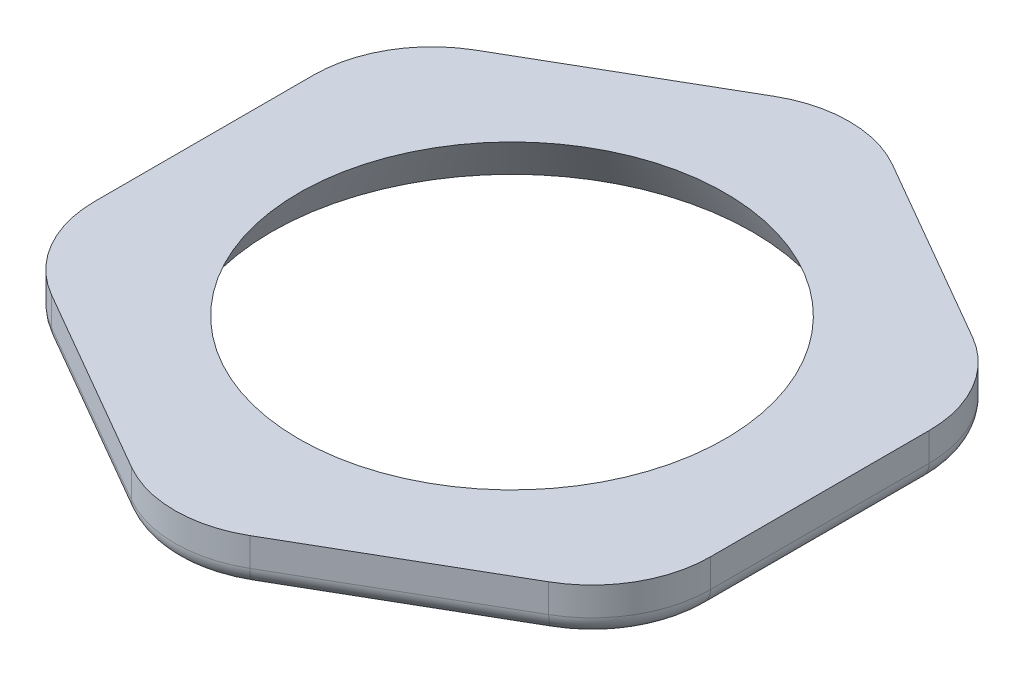
SolidWorks part; units mm, degrees
ref_plane "Front Plane" through (0, 0, 0) normal (0, 0, 1) x (1, 0, 0)
ref_plane "Top Plane" through (0, 0, 0) normal (0, 1, 0) x (1, 0, 0)
ref_plane "Right Plane" through (0, 0, 0) normal (1, 0, 0) x (0, 0, -1)
sketch "Sketch1" plane through (0, 0, 0) normal (0, 1, 0) x (1, 0, 0)
  line L1 (6.5, -2.3094) -> (6.5, 2.3094)
  line L2 (5.25, 4.4745) -> (1.25, 6.7839)
  line L3 (-1.25, 6.7839) -> (-5.25, 4.4745)
  line L4 (-6.5, 2.3094) -> (-6.5, -2.3094)
  line L5 (-5.25, -4.4745) -> (-1.25, -6.7839)
  line L6 (1.25, -6.7839) -> (5.25, -4.4745)
  circle A0 centre (0, 0) radius 6.5 construction
  circle A1 centre (0, 0) radius 4.5
  arc A2 (6.5, 2.3094) -> (5.25, 4.4745) centre (4, 2.3094) ccw
  arc A3 (6.5, -2.3094) -> (5.25, -4.4745) centre (4, -2.3094) cw
  arc A4 (1.25, -6.7839) -> (-1.25, -6.7839) centre (0, -4.6188) cw
  arc A5 (-6.5, -2.3094) -> (-5.25, -4.4745) centre (-4, -2.3094) ccw
  arc A6 (-5.25, 4.4745) -> (-6.5, 2.3094) centre (-4, 2.3094) ccw
  arc A7 (1.25, 6.7839) -> (-1.25, 6.7839) centre (0, 4.6188) ccw
  point P13 (6.5, 3.7528)
  point P16 (6.5, -3.7528)
  point P19 (0, -7.5056)
  dimension "D3" = 2.5
  dimension "D1" = 13
  dimension "D2" = 2
extrude "Boss-Extrude1" add sketch "Sketch1" along normal blind 1
ref_axis "Axis1" through (0, 0, 0) along (0, 1, 0)
ref_plane "Plane3" through (0, 0, 0) normal (-1, 0, 0) x (0, 0, 1)
sketch "Sketch4" plane through (0, 0, 0) normal (-1, 0, 0) x (0, 0, 1)
  line L0 (-7.1188, 0) -> (-7.1188, 0.2135)
  line L1 (-6.9287, 0.8001) -> (-6.7839, 1)
  line L2 (-6.7839, 1) -> (-4.4745, 1) construction
  line L3 (-6.7839, 1) -> (-6.7839, 0) construction
  arc A0 (-6.9287, 0.8001) -> (-7.1188, 0.2135) centre (-6.1188, 0.2135) ccw
  dimension "D1" = 1
  dimension "D2" = 0.8549
sketch "Sketch5" plane through (0, 1, 0) normal (0, 1, 0) x (1, 0, 0)
  circle A0 centre (0, 0) radius 4.5 construction
  circle A1 centre (0, 0) radius 4.5
extrude "Cut-Extrude1" cut sketch "Sketch5" against normal blind 1 draft 30 draft outward yes
fillet "Fillet2" radius 0.4 12 edges at (6.1651, 0, 3.5594) (3.25, 0, 5.6292) (0, 0, 7.1188) (-3.25, 0, 5.6292) (-6.1651, 0, 3.5594) (-6.5, 0, 0) (-6.1651, 0, -3.5594) (-3.25, 0, -5.6292) (0, 0, -7.1188) (3.25, 0, -5.6292) (6.1651, 0, -3.5594) (6.5, 0, 0)
